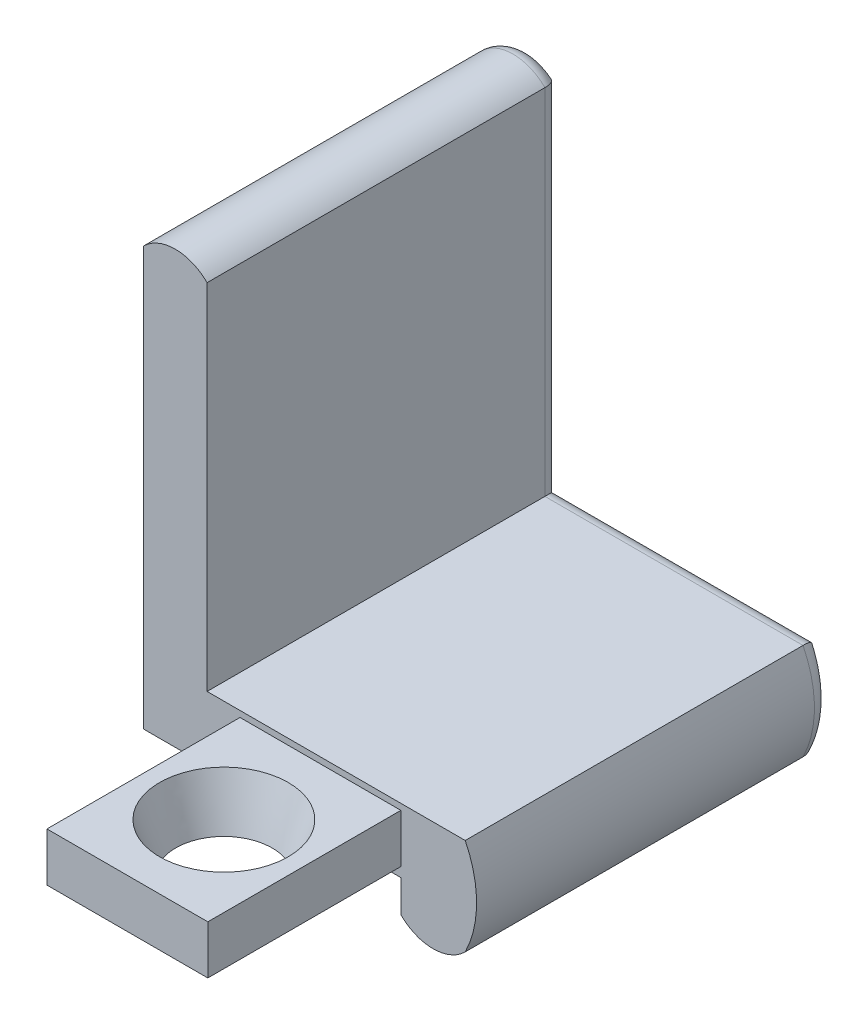
SolidWorks part; units mm, degrees
ref_plane "Front Plane" through (0, 0, 0) normal (0, 0, 1) x (1, 0, 0)
ref_plane "Top Plane" through (0, 0, 0) normal (0, 1, 0) x (1, 0, 0)
ref_plane "Right Plane" through (0, 0, 0) normal (1, 0, 0) x (0, 0, -1)
sketch "Sketch1" plane through (0, 0, 0) normal (0, 0, 1) x (1, 0, 0)
  line L0 (-59.8868, 355.6) -> (-59.8868, 25.4)
  line L1 (-59.8868, 25.4) -> (143.3132, 25.4)
  line L2 (143.3132, 25.4) -> (143.3132, 0)
  line L6 (194.1132, 76.2) -> (-9.6484, 76.2)
  line L7 (-9.6484, 76.2) -> (-9.6484, 355.6875)
  arc A2 (143.3132, 0) -> (194.1132, 0) centre (168.7132, 25.4) ccw
  arc A3 (194.1132, 76.2) -> (194.1132, 0) centre (117.8679, 38.1) cw
  arc A4 (-59.8868, 355.6) -> (-9.6484, 355.6875) centre (-34.7238, 330.5245) cw
  dimension "D1" = 330.2
  dimension "D2" = 25.4
  dimension "D3" = 76.2
  dimension "D5" = 50.8
extrude "Boss-Extrude1" add sketch "Sketch1" along normal blind 279.4
fillet "Fillet1" radius 12.7 8 edges at (-34.7857, 366.0485, 0) (143.3132, 12.7, 0) (168.7132, -10.521, 0) (203.1026, 38.1, 0) (92.2324, 76.2, 0) (41.7132, 25.4, 0) (-59.8868, 190.5, 0) (-9.6484, 215.9437, 0)
sketch "Sketch2" plane through (0, 0, 279.4) normal (0, 0, 1) x (1, 0, 0)
  line L0 (-59.8868, 355.6) -> (-59.8868, 25.4) construction
  line L1 (16.3132, 71.3861) -> (143.3132, 71.3861)
  line L2 (16.3132, 71.3861) -> (16.3132, 32.9675)
  line L3 (16.3132, 32.9675) -> (143.3132, 32.9675)
  line L4 (143.3132, 71.3861) -> (143.3132, 32.9675)
  dimension "D1" = 76.2
  dimension "D2" = 50.8
extrude "Boss-Extrude2" add sketch "Sketch2" along normal blind 152.4
sketch "Sketch3" plane through (0, 71.3861, 0) normal (0, 1, 0) x (1, 0, 0)
  line L0 (143.3132, -431.8) -> (143.3132, -279.4) construction
  line L1 (143.3132, -431.8) -> (16.3132, -431.8) construction
  circle A0 centre (79.8132, -355.6) radius 50.8
  dimension "D1" = 101.6
  dimension "D2" = 63.5
  dimension "D3" = 76.2
sketch "Sketch4" plane through (0, 32.9675, 0) normal (0, -1, 0) x (1, 0, 0)
  circle A0 centre (79.8132, 355.6) radius 38.1
  dimension "D1" = 76.2
loft "Cut-Loft1" cut profiles "Sketch4", "Sketch3" connector at (53.8895, 32.9675, 383.5207) connector at (53.6985, 71.3861, 399.1736)
